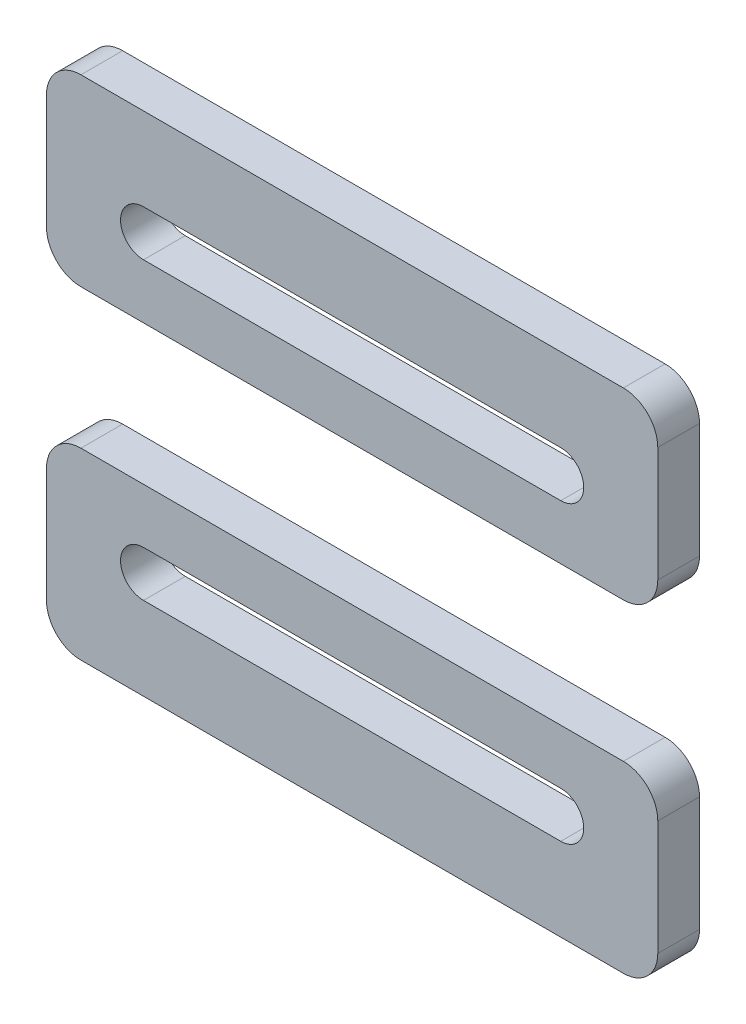
SolidWorks part; units mm, degrees
ref_plane "Alzado" through (0, 0, 0) normal (0, 0, 1) x (1, 0, 0)
ref_plane "Planta" through (0, 0, 0) normal (0, 1, 0) x (1, 0, 0)
ref_plane "Vista lateral" through (0, 0, 0) normal (1, 0, 0) x (0, 0, -1)
sketch "Croquis1" plane through (0, 0, 0) normal (0, 0, 1) x (1, 0, 0)
  line L40 (-24.7839, -5.5176) -> (-24.7839, -11.0176)
  line L41 (-22.7839, -13.0176) -> (3.2161, -13.0176)
  line L42 (5.2161, -11.0176) -> (5.2161, -5.5176)
  line L43 (3.2161, -3.5176) -> (-22.7839, -3.5176)
  line L44 (-19.7839, -10.0476) -> (0.2161, -10.0476)
  line L45 (0.2161, -7.8476) -> (-19.7839, -7.8476)
  line L46 (-19.7839, -24.1876) -> (0.2161, -24.1876)
  line L47 (0.2161, -21.9876) -> (-19.7839, -21.9876)
  line L48 (5.2161, -26.5176) -> (5.2161, -21.0176)
  line L49 (3.2161, -19.0176) -> (-22.7839, -19.0176)
  line L50 (-24.7839, -21.0176) -> (-24.7839, -26.5176)
  line L51 (-22.7839, -28.5176) -> (3.2161, -28.5176)
  arc A40 (-24.7839, -11.0176) -> (-22.7839, -13.0176) centre (-22.7839, -11.0176) ccw
  arc A41 (3.2161, -13.0176) -> (5.2161, -11.0176) centre (3.2161, -11.0176) ccw
  arc A42 (5.2161, -5.5176) -> (3.2161, -3.5176) centre (3.2161, -5.5176) ccw
  arc A43 (-22.7839, -3.5176) -> (-24.7839, -5.5176) centre (-22.7839, -5.5176) ccw
  arc A44 (0.2161, -10.0476) -> (0.2161, -7.8476) centre (0.2161, -8.9476) ccw
  arc A45 (-19.7839, -7.8476) -> (-19.7839, -10.0476) centre (-19.7839, -8.9476) ccw
  arc A46 (0.2161, -24.1876) -> (0.2161, -21.9876) centre (0.2161, -23.0876) ccw
  arc A47 (-19.7839, -21.9876) -> (-19.7839, -24.1876) centre (-19.7839, -23.0876) ccw
  arc A48 (5.2161, -21.0176) -> (3.2161, -19.0176) centre (3.2161, -21.0176) ccw
  arc A49 (-22.7839, -19.0176) -> (-24.7839, -21.0176) centre (-22.7839, -21.0176) ccw
  arc A50 (-24.7839, -26.5176) -> (-22.7839, -28.5176) centre (-22.7839, -26.5176) ccw
  arc A51 (3.2161, -28.5176) -> (5.2161, -26.5176) centre (3.2161, -26.5176) ccw
extrude "Saliente-Extruir1" add sketch "Croquis1" along normal blind 2 contours L40 A40 L41 A41 L42 A42 L43 A43 | L48 A48 L49 A49 L50 A50 L51 A51 | L44 A44 L45 A45 | L46 A46 L47 A47
sketch "Croquis2" plane through (0, 0, 2) normal (0, 0, 1) x (1, 0, 0)
  line L12 (5.2161, -26.5176) -> (5.2161, -21.0176)
  line L13 (3.2161, -19.0176) -> (-22.7839, -19.0176)
  line L14 (-24.7839, -21.0176) -> (-24.7839, -26.5176)
  line L15 (-22.7839, -28.5176) -> (3.2161, -28.5176)
  line L16 (5.2161, -26.5176) -> (5.2161, -21.0176)
  line L17 (3.2161, -19.0176) -> (-22.7839, -19.0176)
  line L18 (-24.7839, -21.0176) -> (-24.7839, -26.5176)
  line L19 (-22.7839, -28.5176) -> (3.2161, -28.5176)
  line L24 (-24.7839, -5.5176) -> (-24.7839, -11.0176)
  line L25 (-22.7839, -13.0176) -> (3.2161, -13.0176)
  line L26 (5.2161, -11.0176) -> (5.2161, -5.5176)
  line L27 (3.2161, -3.5176) -> (-22.7839, -3.5176)
  line L28 (-24.7839, -5.5176) -> (-24.7839, -11.0176)
  line L29 (-22.7839, -13.0176) -> (3.2161, -13.0176)
  line L30 (5.2161, -11.0176) -> (5.2161, -5.5176)
  line L31 (3.2161, -3.5176) -> (-22.7839, -3.5176)
  line L36 (4.8661, -26.5176) -> (4.8661, -21.0176)
  line L37 (3.2161, -19.3676) -> (-22.7839, -19.3676)
  line L38 (-24.4339, -21.0176) -> (-24.4339, -26.5176)
  line L39 (-22.7839, -28.1676) -> (3.2161, -28.1676)
  line L40 (4.8661, -26.5176) -> (4.8661, -21.0176)
  line L41 (3.2161, -19.3676) -> (-22.7839, -19.3676)
  line L42 (-24.4339, -21.0176) -> (-24.4339, -26.5176)
  line L43 (-22.7839, -28.1676) -> (3.2161, -28.1676)
  line L48 (-24.4339, -5.5176) -> (-24.4339, -11.0176)
  line L49 (-22.7839, -12.6676) -> (3.2161, -12.6676)
  line L50 (4.8661, -11.0176) -> (4.8661, -5.5176)
  line L51 (3.2161, -3.8676) -> (-22.7839, -3.8676)
  line L52 (-24.4339, -5.5176) -> (-24.4339, -11.0176)
  line L53 (-22.7839, -12.6676) -> (3.2161, -12.6676)
  line L54 (4.8661, -11.0176) -> (4.8661, -5.5176)
  line L55 (3.2161, -3.8676) -> (-22.7839, -3.8676)
  arc A12 (3.2161, -28.5176) -> (5.2161, -26.5176) centre (3.2161, -26.5176) ccw
  arc A13 (5.2161, -21.0176) -> (3.2161, -19.0176) centre (3.2161, -21.0176) ccw
  arc A14 (-22.7839, -19.0176) -> (-24.7839, -21.0176) centre (-22.7839, -21.0176) ccw
  arc A15 (-24.7839, -26.5176) -> (-22.7839, -28.5176) centre (-22.7839, -26.5176) ccw
  arc A16 (3.2161, -28.5176) -> (5.2161, -26.5176) centre (3.2161, -26.5176) ccw
  arc A17 (5.2161, -21.0176) -> (3.2161, -19.0176) centre (3.2161, -21.0176) ccw
  arc A18 (-22.7839, -19.0176) -> (-24.7839, -21.0176) centre (-22.7839, -21.0176) ccw
  arc A19 (-24.7839, -26.5176) -> (-22.7839, -28.5176) centre (-22.7839, -26.5176) ccw
  arc A24 (-22.7839, -3.5176) -> (-24.7839, -5.5176) centre (-22.7839, -5.5176) ccw
  arc A25 (-24.7839, -11.0176) -> (-22.7839, -13.0176) centre (-22.7839, -11.0176) ccw
  arc A26 (3.2161, -13.0176) -> (5.2161, -11.0176) centre (3.2161, -11.0176) ccw
  arc A27 (5.2161, -5.5176) -> (3.2161, -3.5176) centre (3.2161, -5.5176) ccw
  arc A28 (-22.7839, -3.5176) -> (-24.7839, -5.5176) centre (-22.7839, -5.5176) ccw
  arc A29 (-24.7839, -11.0176) -> (-22.7839, -13.0176) centre (-22.7839, -11.0176) ccw
  arc A30 (3.2161, -13.0176) -> (5.2161, -11.0176) centre (3.2161, -11.0176) ccw
  arc A31 (5.2161, -5.5176) -> (3.2161, -3.5176) centre (3.2161, -5.5176) ccw
  arc A36 (3.2161, -28.1676) -> (4.8661, -26.5176) centre (3.2161, -26.5176) ccw
  arc A37 (4.8661, -21.0176) -> (3.2161, -19.3676) centre (3.2161, -21.0176) ccw
  arc A38 (-22.7839, -19.3676) -> (-24.4339, -21.0176) centre (-22.7839, -21.0176) ccw
  arc A39 (-24.4339, -26.5176) -> (-22.7839, -28.1676) centre (-22.7839, -26.5176) ccw
  arc A40 (3.2161, -28.1676) -> (4.8661, -26.5176) centre (3.2161, -26.5176) ccw
  arc A41 (4.8661, -21.0176) -> (3.2161, -19.3676) centre (3.2161, -21.0176) ccw
  arc A42 (-22.7839, -19.3676) -> (-24.4339, -21.0176) centre (-22.7839, -21.0176) ccw
  arc A43 (-24.4339, -26.5176) -> (-22.7839, -28.1676) centre (-22.7839, -26.5176) ccw
  arc A48 (-22.7839, -3.8676) -> (-24.4339, -5.5176) centre (-22.7839, -5.5176) ccw
  arc A49 (-24.4339, -11.0176) -> (-22.7839, -12.6676) centre (-22.7839, -11.0176) ccw
  arc A50 (3.2161, -12.6676) -> (4.8661, -11.0176) centre (3.2161, -11.0176) ccw
  arc A51 (4.8661, -5.5176) -> (3.2161, -3.8676) centre (3.2161, -5.5176) ccw
  arc A52 (-22.7839, -3.8676) -> (-24.4339, -5.5176) centre (-22.7839, -5.5176) ccw
  arc A53 (-24.4339, -11.0176) -> (-22.7839, -12.6676) centre (-22.7839, -11.0176) ccw
  arc A54 (3.2161, -12.6676) -> (4.8661, -11.0176) centre (3.2161, -11.0176) ccw
  arc A55 (4.8661, -5.5176) -> (3.2161, -3.8676) centre (3.2161, -5.5176) ccw
  dimension "D1" = 0
  dimension "D2" = 0
  dimension "D3" = 0.35
  dimension "D4" = 0.35
extrude "Cortar-Extruir1" cut sketch "Croquis2" against normal up to surface (2 mm away) up to face at (-9.7839, -23.7676, 0)
